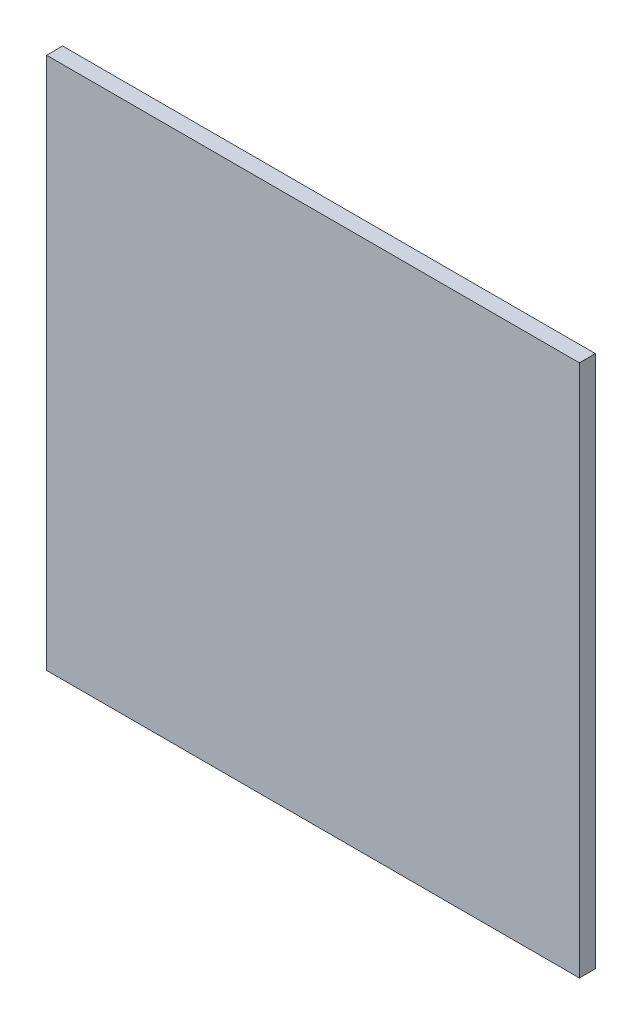
SolidWorks part; units mm, degrees
ref_plane "Спереди" through (0, 0, 0) normal (0, 0, 1) x (1, 0, 0)
ref_plane "Сверху" through (0, 0, 0) normal (0, 1, 0) x (1, 0, 0)
ref_plane "Справа" through (0, 0, 0) normal (1, 0, 0) x (0, 0, -1)
sketch "Эскиз1" plane through (0, 0, 0) normal (0, 0, 1) x (1, 0, 0)
  line L1 (-300, 300) -> (300, 300)
  line L2 (-300, 300) -> (-300, -300)
  line L3 (-300, -300) -> (300, -300)
  line L4 (300, 300) -> (300, -300)
  line L5 (-300, 300) -> (300, -300) construction
  line L6 (-300, -300) -> (300, 300) construction
  point P0 (0, 0)
extrude "Бобышка-Вытянуть1" add sketch "Эскиз1" along normal blind 18
